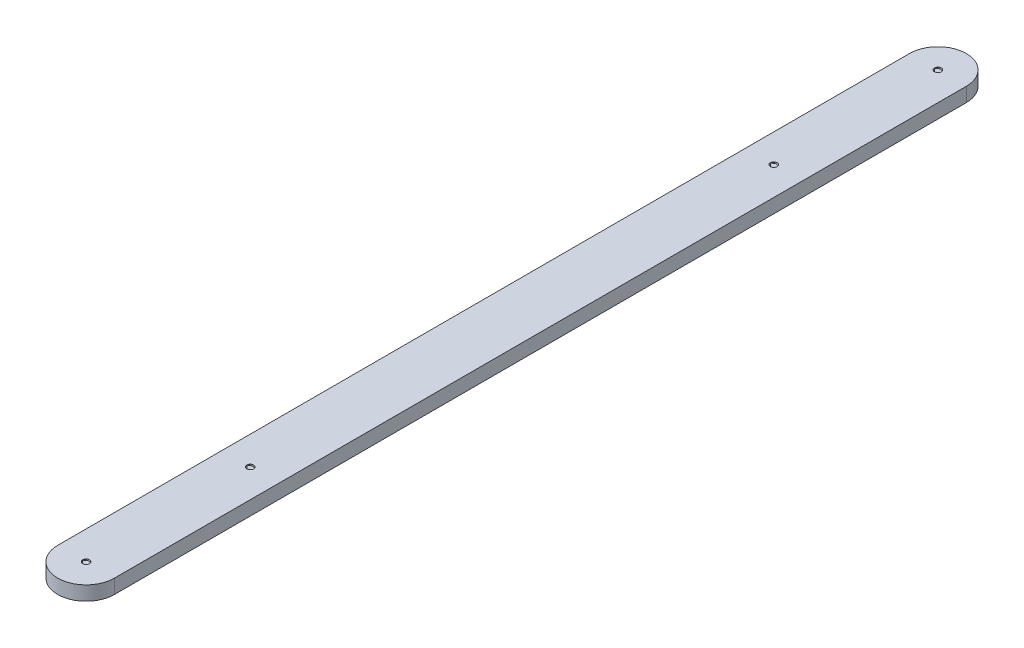
SolidWorks part; units mm, degrees
material "PVC 0.007 Plasticized"
ref_plane "Front Plane" through (0, 0, 0) normal (0, 0, 1) x (1, 0, 0)
ref_plane "Top Plane" through (0, 0, 0) normal (0, 1, 0) x (1, 0, 0)
ref_plane "Right Plane" through (0, 0, 0) normal (1, 0, 0) x (0, 0, -1)
sketch "Sketch1" plane through (0, 0, 0) normal (0, 1, 0) x (1, 0, 0)
  line L2 (-5, -75) -> (-5, 75)
  line L4 (5, -75) -> (5, 75)
  line L5 (-5, -75) -> (-1.4594, -21.891) construction
  line L6 (0, 0) -> (5, -75) construction
  arc A0 (5, 75) -> (-5, 75) centre (0, 75) ccw
  arc A2 (5, -75) -> (-5, -75) centre (0, -75) cw
  point P0 (0, 0)
  dimension "D1" = 150
extrude "Boss-Extrude1" add sketch "Sketch1" along normal blind 2.5
sketch "Sketch2" plane through (0, 2.5, 0) normal (0, 1, 0) x (1, 0, 0)
  circle A0 centre (0, 75) radius 0.6
  circle A1 centre (0, 46.1) radius 0.6
  circle A2 centre (0, -46.1) radius 0.6
  circle A3 centre (0, -75) radius 0.6
  dimension "D2" = 1.2
  dimension "D3" = 1.2
  dimension "D4" = 1.2
  dimension "D5" = 1.2
  dimension "D1" = 28.9
  dimension "D6" = 28.9
extrude "Cut-Extrude1" cut sketch "Sketch2" against normal blind 10
thread "Thread1" pitch 1.25 method cut profile "Thread Profile2" start angle 0, offset 0, length 10, pitch 1.25, diameter 1.2
ref_plane "Plane2" through (-0.6, 2.5, 75) normal (0, 0, 1) x (-1, 0, 0)
sketch "Thread Profile2" plane through (-0.6, 2.5, 75) normal (0, 0, 1) x (-1, 0, 0)
  line L0 (0, 0) -> (0, 1.25) construction
  line L1 (0, 0) -> (0.6766, 0.3906)
  line L2 (0.6766, 0.3906) -> (0.6766, 0.5469)
  line L3 (0.6766, 0.5469) -> (0, 0.9375)
  line L4 (0.6766, 0.4687) -> (0, 0.4687) construction
  line L11 (0, 0) -> (0, 0.9375)
  point P2 (0, 0)
  dimension "Pitch" = 1.25
  dimension "Profile_Angle" = 60
  dimension "Profile_Land" = 0.1562
  dimension "Profile_Height" = 0.6766
thread "Thread2" pitch 1.25 method cut profile "Thread Profile3" start angle 0, offset 0, length 10, pitch 1.25, diameter 1.2
ref_plane "Plane3" through (-0.6, 2.5, 46.1) normal (0, 0, 1) x (-1, 0, 0)
sketch "Thread Profile3" plane through (-0.6, 2.5, 46.1) normal (0, 0, 1) x (-1, 0, 0)
  line L0 (0, 0) -> (0, 1.25) construction
  line L1 (0, 0) -> (0.6766, 0.3906)
  line L2 (0.6766, 0.3906) -> (0.6766, 0.5469)
  line L3 (0.6766, 0.5469) -> (0, 0.9375)
  line L4 (0.6766, 0.4687) -> (0, 0.4687) construction
  line L11 (0, 0) -> (0, 0.9375)
  point P2 (0, 0)
  dimension "Pitch" = 1.25
  dimension "Profile_Angle" = 60
  dimension "Profile_Land" = 0.1562
  dimension "Profile_Height" = 0.6766
thread "Thread3" pitch 1.25 method cut profile "Thread Profile4" start angle 0, offset 0, length 10, pitch 1.25, diameter 1.2
ref_plane "Plane4" through (-0.6, 2.5, -46.1) normal (0, 0, 1) x (-1, 0, 0)
sketch "Thread Profile4" plane through (-0.6, 2.5, -46.1) normal (0, 0, 1) x (-1, 0, 0)
  line L0 (0, 0) -> (0, 1.25) construction
  line L1 (0, 0) -> (0.6766, 0.3906)
  line L2 (0.6766, 0.3906) -> (0.6766, 0.5469)
  line L3 (0.6766, 0.5469) -> (0, 0.9375)
  line L4 (0.6766, 0.4687) -> (0, 0.4687) construction
  line L11 (0, 0) -> (0, 0.9375)
  point P2 (0, 0)
  dimension "Pitch" = 1.25
  dimension "Profile_Angle" = 60
  dimension "Profile_Land" = 0.1562
  dimension "Profile_Height" = 0.6766
thread "Thread4" pitch 1.25 method cut profile "Thread Profile5" start angle 0, offset 0, length 20, pitch 1.25, diameter 1.2
ref_plane "Plane5" through (-0.6, 2.5, -75) normal (0, 0, 1) x (-1, 0, 0)
sketch "Thread Profile5" plane through (-0.6, 2.5, -75) normal (0, 0, 1) x (-1, 0, 0)
  line L0 (0, 0) -> (0, 1.25) construction
  line L1 (0, 0) -> (0.6766, 0.3906)
  line L2 (0.6766, 0.3906) -> (0.6766, 0.5469)
  line L3 (0.6766, 0.5469) -> (0, 0.9375)
  line L4 (0.6766, 0.4687) -> (0, 0.4687) construction
  line L11 (0, 0) -> (0, 0.9375)
  point P2 (0, 0)
  dimension "Pitch" = 1.25
  dimension "Profile_Angle" = 60
  dimension "Profile_Land" = 0.1562
  dimension "Profile_Height" = 0.6766
